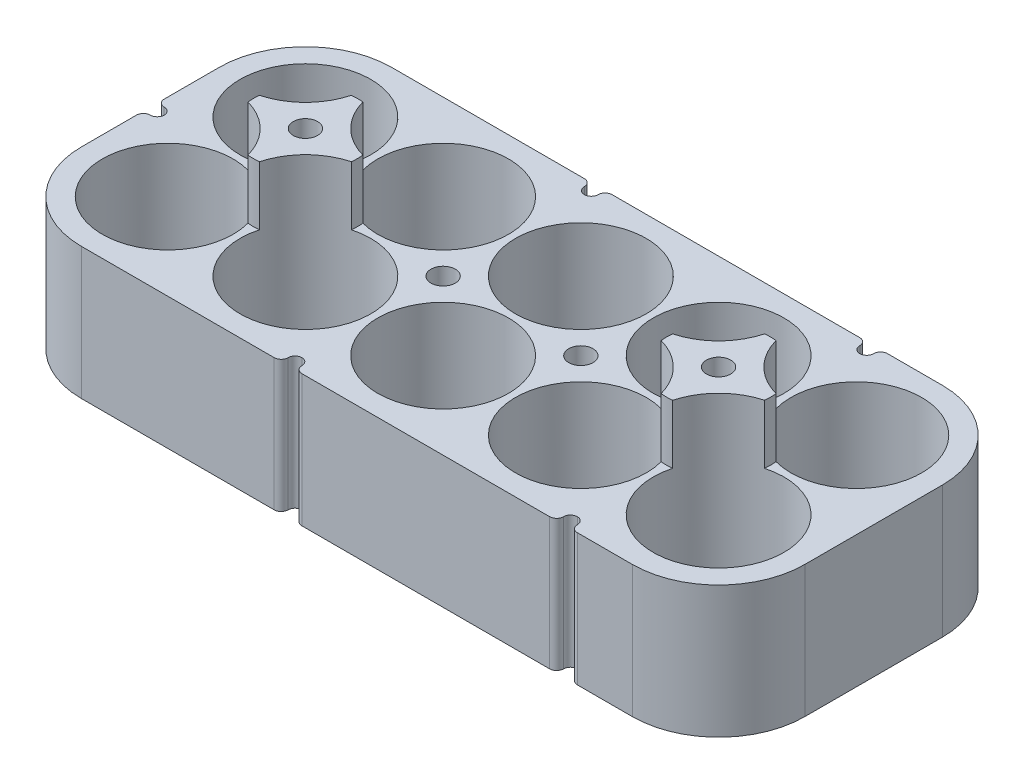
SolidWorks part; units mm, degrees
ref_plane "Front Plane" through (0, 0, 0) normal (0, 0, 1) x (1, 0, 0)
ref_plane "Top Plane" through (0, 0, 0) normal (0, 1, 0) x (1, 0, 0)
ref_plane "Right Plane" through (0, 0, 0) normal (1, 0, 0) x (0, 0, -1)
sketch "Sketch2" plane through (0, 0, 0) normal (0, 1, 0) x (1, 0, 0)
  line L0 (-39.7, 9.925) -> (-19.85, 9.925) construction
  line L1 (-19.85, 9.925) -> (0, 9.925) construction
  line L2 (0, 9.925) -> (19.85, 9.925) construction
  line L3 (19.85, 9.925) -> (39.7, 9.925) construction
  line L4 (39.7, 9.925) -> (39.7, -9.925) construction
  line L5 (39.7, -9.925) -> (19.85, -9.925) construction
  line L6 (19.85, -9.925) -> (0, -9.925) construction
  line L7 (0, -9.925) -> (-19.85, -9.925) construction
  line L8 (-39.7, 9.925) -> (-39.7, -9.925) construction
  line L9 (-39.7, -9.925) -> (-19.85, -9.925) construction
  line L10 (-39.7, 9.925) -> (39.7, -9.925) construction
  line L11 (-30.275, 9.925) -> (-29.275, 9.925) construction
  line L16 (-39.7, 0.5) -> (-39.7, -0.5) construction
  line L17 (-39.7, 22.35) -> (39.7, 22.35)
  line L19 (52.125, -9.925) -> (52.125, 9.925)
  line L20 (39.7, -22.35) -> (-39.7, -22.35)
  line L21 (-52.125, -9.925) -> (-52.125, 9.925)
  line L22 (-39.7, -9.925) -> (-52.125, -9.925) construction
  circle A0 centre (-39.7, 9.925) radius 9.425
  circle A1 centre (-19.85, 9.925) radius 9.425
  circle A2 centre (-39.7, -9.925) radius 9.425
  circle A3 centre (-19.85, -9.925) radius 9.425
  circle A4 centre (0, 9.925) radius 9.425
  circle A5 centre (0, -9.925) radius 9.425
  circle A6 centre (19.85, 9.925) radius 9.425
  circle A7 centre (19.85, -9.925) radius 9.425
  circle A8 centre (39.7, 9.925) radius 9.425
  circle A9 centre (39.7, -9.925) radius 9.425
  circle A10 centre (-39.7, 9.925) radius 12.425
  circle A11 centre (-39.7, -9.925) radius 12.425
  circle A12 centre (39.7, -9.925) radius 12.425
  circle A13 centre (39.7, 9.925) radius 12.425
  dimension "D1" = 18.85
  dimension "D2" = 1
  dimension "D3" = 1
  dimension "D4" = 3
extrude "Boss-Extrude1" add sketch "Sketch2" along normal blind 2.5 contours A13 L17 A10 A1 A11 A3 L20 A12 A7 A6 A5 A4 | A12 A13 A6 A8 | A13 A9 A12 A7 | A13 A12 L19 | A9 A13 A12 A8 | A11 A10 L21 | A11 A10 A1 A0 | A3 A11 A10 A2 | A10 A11 A0 A2 region at (-32.8744, 0, -19.9125) region at (0, 0, 0) region at (48.2539, 0, -18.4789) region at (-50.7094, 0, 0) region at (50.7094, 0, 0) region at (-50.5254, 0, 4.5259) region at (-39.7, 0, 0) region at (48.2539, 0, 18.4789) region at (39.7, 0, 0)
sketch "Sketch7" plane through (0, 0, 0) normal (0, 1, 0) x (1, 0, 0)
  line L0 (-29.775, 0) -> (-9.925, 0) construction
  line L1 (-9.925, 0) -> (9.925, 0) construction
  line L2 (9.925, 0) -> (29.775, 0) construction
  circle A1 centre (-29.775, 0) radius 3
  circle A2 centre (-9.925, 0) radius 1.75
  circle A3 centre (9.925, 0) radius 1.75
  circle A4 centre (29.775, 0) radius 3
  circle A5 centre (-29.775, 0) radius 4.6111 construction
  circle A7 centre (-39.7, 9.925) radius 9.425 construction
  circle A8 centre (-19.85, -9.925) radius 9.425 construction
  dimension "D1" = 6
  dimension "D2" = 3.5
extrude "Cut-Extrude3" cut sketch "Sketch7" along normal through all both and the other way through all
sketch "Sketch9" plane through (0, 2.5, 0) normal (0, 1, 0) x (1, 0, 0)
  line L0 (39.7, -22.35) -> (-39.7, -22.35)
  line L1 (-52.125, -9.925) -> (-52.125, 9.925)
  line L2 (-39.7, 22.35) -> (39.7, 22.35)
  line L3 (52.125, 9.925) -> (52.125, -9.925)
  line L4 (6.4609, 0) -> (-6.4609, 0) construction
  line L5 (6.4609, 0) -> (8.1929, -3)
  line L6 (8.1929, -3) -> (11.6571, -3)
  line L7 (11.6571, -3) -> (13.3891, 0)
  line L8 (13.3891, 0) -> (11.6571, 3)
  line L9 (11.6571, 3) -> (8.1929, 3)
  line L10 (8.1929, 3) -> (6.4609, 0)
  line L11 (-6.4609, 0) -> (-8.1929, 3)
  line L12 (-8.1929, 3) -> (-11.6571, 3)
  line L13 (-11.6571, 3) -> (-13.3891, 0)
  line L14 (-13.3891, 0) -> (-11.6571, -3)
  line L15 (-11.6571, -3) -> (-8.1929, -3)
  line L16 (-8.1929, -3) -> (-6.4609, 0)
  circle A0 centre (39.7, -9.925) radius 9.425
  circle A1 centre (19.85, -9.925) radius 9.425
  circle A2 centre (0, -9.925) radius 9.425
  circle A3 centre (-19.85, -9.925) radius 9.425
  circle A4 centre (-39.7, -9.925) radius 9.425
  circle A5 centre (-39.7, 9.925) radius 9.425
  circle A6 centre (-19.85, 9.925) radius 9.425
  circle A7 centre (0, 9.925) radius 9.425
  circle A8 centre (19.85, 9.925) radius 9.425
  circle A9 centre (39.7, 9.925) radius 9.425
  circle A10 centre (39.7, 9.925) radius 9.425 construction
  circle A11 centre (19.85, 9.925) radius 9.425 construction
  circle A12 centre (0, 9.925) radius 9.425 construction
  circle A13 centre (-19.85, 9.925) radius 9.425 construction
  circle A14 centre (-39.7, 9.925) radius 9.425 construction
  circle A15 centre (39.7, -9.925) radius 9.425 construction
  circle A16 centre (19.85, -9.925) radius 9.425 construction
  circle A17 centre (0, -9.925) radius 9.425 construction
  circle A18 centre (-19.85, -9.925) radius 9.425 construction
  circle A19 centre (-39.7, -9.925) radius 9.425 construction
  arc A20 (52.125, -9.925) -> (39.7, -22.35) centre (39.7, -9.925) cw
  arc A21 (-52.125, -9.925) -> (-39.7, -22.35) centre (-39.7, -9.925) ccw
  arc A22 (-52.125, 9.925) -> (-39.7, 22.35) centre (-39.7, 9.925) cw
  arc A23 (39.7, 22.35) -> (52.125, 9.925) centre (39.7, 9.925) cw
  circle A24 centre (29.775, 0) radius 3
  circle A25 centre (-29.775, 0) radius 3
  circle A26 centre (29.775, 0) radius 3 construction
  circle A27 centre (-29.775, 0) radius 3 construction
  circle A28 centre (9.925, 0) radius 3 construction
  circle A29 centre (9.925, 0) radius 1.75 construction
  circle A30 centre (-9.925, 0) radius 3 construction
  circle A31 centre (-9.925, 0) radius 1.75 construction
  dimension "D1" = 6
extrude "Boss-Extrude2" add sketch "Sketch9" along normal blind 3
sketch "Sketch11" plane through (0, 5.5, 0) normal (0, 1, 0) x (1, 0, 0)
  line L4 (39.7, -22.35) -> (-39.7, -22.35)
  line L17 (-52.125, -9.925) -> (-52.125, 9.925)
  line L18 (-39.7, 22.35) -> (39.7, 22.35)
  line L19 (52.125, 9.925) -> (52.125, -9.925)
  circle A10 centre (39.7, -9.925) radius 9.425
  circle A11 centre (19.85, -9.925) radius 9.425
  circle A12 centre (0, -9.925) radius 9.425
  circle A13 centre (-19.85, -9.925) radius 9.425
  circle A14 centre (-39.7, -9.925) radius 9.425
  circle A15 centre (-39.7, 9.925) radius 9.425
  circle A16 centre (-19.85, 9.925) radius 9.425
  circle A17 centre (0, 9.925) radius 9.425
  circle A18 centre (19.85, 9.925) radius 9.425
  circle A19 centre (39.7, 9.925) radius 9.425
  circle A26 centre (29.775, 0) radius 3
  circle A27 centre (-29.775, 0) radius 3
  circle A28 centre (-9.925, 0) radius 1.75
  circle A29 centre (9.925, 0) radius 1.75
  circle A30 centre (39.7, -9.925) radius 9.425 construction
  circle A31 centre (19.85, -9.925) radius 9.425 construction
  circle A32 centre (0, -9.925) radius 9.425 construction
  circle A33 centre (-19.85, -9.925) radius 9.425 construction
  circle A34 centre (-39.7, -9.925) radius 9.425 construction
  circle A35 centre (-39.7, 9.925) radius 9.425 construction
  circle A36 centre (-19.85, 9.925) radius 9.425 construction
  circle A37 centre (0, 9.925) radius 9.425 construction
  circle A38 centre (19.85, 9.925) radius 9.425 construction
  circle A39 centre (39.7, 9.925) radius 9.425 construction
  circle A40 centre (29.775, 0) radius 3 construction
  circle A41 centre (9.925, 0) radius 1.75 construction
  circle A42 centre (-9.925, 0) radius 1.75 construction
  circle A43 centre (-29.775, 0) radius 3 construction
  arc A44 (39.7, -22.35) -> (52.125, -9.925) centre (39.7, -9.925) ccw
  arc A45 (52.125, 9.925) -> (39.7, 22.35) centre (39.7, 9.925) ccw
  arc A46 (-39.7, 22.35) -> (-52.125, 9.925) centre (-39.7, 9.925) ccw
  arc A47 (-52.125, -9.925) -> (-39.7, -22.35) centre (-39.7, -9.925) ccw
extrude "Boss-Extrude3" add sketch "Sketch11" along normal blind 6
sketch "Sketch12" plane through (0, 11.5, 0) normal (0, 1, 0) x (1, 0, 0)
  line L0 (39.7, -22.35) -> (-39.7, -22.35)
  line L1 (-52.125, -9.925) -> (-52.125, 9.925)
  line L2 (-39.7, 22.35) -> (39.7, 22.35)
  line L3 (52.125, 9.925) -> (52.125, -9.925)
  circle A0 centre (39.7, -9.925) radius 9.425
  circle A1 centre (19.85, -9.925) radius 9.425
  circle A2 centre (0, -9.925) radius 9.425
  circle A3 centre (-19.85, -9.925) radius 9.425
  circle A4 centre (-39.7, -9.925) radius 9.425
  circle A5 centre (-39.7, 9.925) radius 9.425
  circle A6 centre (-19.85, 9.925) radius 9.425
  circle A7 centre (0, 9.925) radius 9.425
  circle A8 centre (19.85, 9.925) radius 9.425
  circle A9 centre (39.7, 9.925) radius 9.425
  circle A10 centre (39.7, 9.925) radius 9.425 construction
  circle A11 centre (19.85, 9.925) radius 9.425 construction
  circle A12 centre (0, 9.925) radius 9.425 construction
  circle A13 centre (-19.85, 9.925) radius 9.425 construction
  circle A14 centre (-39.7, 9.925) radius 9.425 construction
  circle A15 centre (39.7, -9.925) radius 9.425 construction
  circle A16 centre (19.85, -9.925) radius 9.425 construction
  circle A17 centre (0, -9.925) radius 9.425 construction
  circle A18 centre (-19.85, -9.925) radius 9.425 construction
  circle A19 centre (-39.7, -9.925) radius 9.425 construction
  circle A20 centre (29.775, 0) radius 1.75
  circle A21 centre (9.925, 0) radius 1.75
  circle A22 centre (-9.925, 0) radius 1.75
  circle A23 centre (-29.775, 0) radius 1.75
  circle A24 centre (9.925, 0) radius 1.75 construction
  circle A25 centre (-9.925, 0) radius 1.75 construction
  circle A26 centre (29.775, 0) radius 3 construction
  circle A27 centre (-29.775, 0) radius 3 construction
  arc A28 (39.7, -22.35) -> (52.125, -9.925) centre (39.7, -9.925) ccw
  arc A29 (52.125, 9.925) -> (39.7, 22.35) centre (39.7, 9.925) ccw
  arc A30 (-39.7, 22.35) -> (-52.125, 9.925) centre (-39.7, 9.925) ccw
  arc A31 (-52.125, -9.925) -> (-39.7, -22.35) centre (-39.7, -9.925) ccw
extrude "Boss-Extrude4" add sketch "Sketch12" along normal blind 16
ref_plane "Plane1" through (0, 22.5, 0) normal (0, 1, 0) x (1, 0, 0)
sketch "Sketch13" plane through (0, 22.5, 0) normal (0, 1, 0) x (1, 0, 0)
  line L0 (-26.3109, 0) -> (26.3109, 0) construction
  line L1 (-28.0429, -3) -> (-26.3109, 0)
  line L2 (-26.3109, 0) -> (-28.0429, 3)
  line L3 (-28.0429, 3) -> (-31.5071, 3)
  line L4 (-31.5071, 3) -> (-33.2391, 0)
  line L5 (-33.2391, 0) -> (-31.5071, -3)
  line L6 (-31.5071, -3) -> (-28.0429, -3)
  line L7 (28.0429, -3) -> (31.5071, -3)
  line L8 (31.5071, -3) -> (33.2391, 0)
  line L9 (33.2391, 0) -> (31.5071, 3)
  line L10 (31.5071, 3) -> (28.0429, 3)
  line L11 (28.0429, 3) -> (26.3109, 0)
  line L12 (26.3109, 0) -> (28.0429, -3)
  circle A0 centre (-29.775, 0) radius 3 construction
  circle A1 centre (29.775, 0) radius 3 construction
  dimension "D1" = 6
extrude "Cut-Extrude4" cut sketch "Sketch13" against normal blind 3
sketch "Sketch14" plane through (0, 27.5, 0) normal (0, 1, 0) x (1, 0, 0)
  line L0 (-52.125, 9.925) -> (-52.125, -9.925) construction
  line L1 (-52.125, 1) -> (-50.125, 1)
  line L2 (-52.125, 1) -> (-52.125, -1)
  line L3 (-52.125, -1) -> (-50.125, -1)
  line L4 (-50.125, 1) -> (-50.125, -1)
  line L5 (-39.7, -22.35) -> (39.7, -22.35) construction
  line L6 (28.775, -22.35) -> (30.775, -22.35)
  line L7 (28.775, -22.35) -> (28.775, -20.35)
  line L8 (28.775, -20.35) -> (30.775, -20.35)
  line L9 (30.775, -22.35) -> (30.775, -20.35)
  line L10 (39.7, 22.35) -> (-39.7, 22.35) construction
  line L11 (-10.925, -22.35) -> (-8.925, -22.35)
  line L12 (-10.925, -22.35) -> (-10.925, -20.35)
  line L13 (-10.925, -20.35) -> (-8.925, -20.35)
  line L14 (-8.925, -22.35) -> (-8.925, -20.35)
  line L15 (-10.925, 22.35) -> (-8.925, 22.35)
  line L16 (-10.925, 22.35) -> (-10.925, 20.35)
  line L17 (-10.925, 20.35) -> (-8.925, 20.35)
  line L18 (-8.925, 22.35) -> (-8.925, 20.35)
  line L19 (-9.925, 0) -> (-9.925, -20.35) construction
  line L20 (28.775, 22.35) -> (30.775, 22.35)
  line L21 (28.775, 22.35) -> (28.775, 20.35)
  line L22 (28.775, 20.35) -> (30.775, 20.35)
  line L23 (30.775, 22.35) -> (30.775, 20.35)
  line L24 (-9.925, 0) -> (-9.925, 20.35) construction
  line L25 (29.775, 0) -> (29.775, 20.35) construction
  line L26 (29.775, 0) -> (29.775, -20.35) construction
  line L27 (-50.125, 0) -> (-29.775, 0) construction
  dimension "D1" = 2
  dimension "D2" = 2
extrude "Cut-Extrude5" cut sketch "Sketch14" against normal through all
fillet "Fillet1" radius 1 30 edges at (28.775, 27.5, -21.35) (30.775, 27.5, -21.35) (-10.925, 27.5, -21.35) (-8.925, 27.5, -21.35) (-51.125, 27.5, 1) (-51.125, 27.5, -1) (30.775, 27.5, 21.35) (28.775, 27.5, 21.35) (-8.925, 27.5, 21.35) (-10.925, 27.5, 21.35) (28.775, 13.75, -20.35) (30.775, 13.75, -20.35) (-10.925, 13.75, -20.35) (-8.925, 13.75, -20.35) (-50.125, 13.75, 1) (-50.125, 13.75, -1) (30.775, 13.75, 20.35) (28.775, 13.75, 20.35) (30.775, 13.75, -22.35) (28.775, 13.75, -22.35) (-8.925, 13.75, -22.35) (-10.925, 13.75, -22.35) (-52.125, 13.75, 1) (-52.125, 13.75, -1) (30.775, 13.75, 22.35) (28.775, 13.75, 22.35) (-8.925, 13.75, 22.35) (-8.925, 13.75, 20.35) (-10.925, 13.75, 20.35) (-10.925, 13.75, 22.35)
ref_plane "Plane2" through (0, 19, 0) normal (0, 1, 0) x (1, 0, 0)
sketch "Sketch15" plane through (0, 19, 0) normal (0, 1, 0) x (1, 0, 0)
  line L0 (-52.125, 9.925) -> (-52.125, 2) construction
  line L1 (-52.125, 22.35) -> (52.125, 22.35)
  line L2 (-52.125, 22.35) -> (-52.125, -22.35)
  line L3 (-52.125, -22.35) -> (52.125, -22.35)
  line L4 (52.125, 22.35) -> (52.125, -22.35)
  line L5 (52.125, -9.925) -> (52.125, 9.925) construction
  line L6 (27.775, 22.35) -> (-7.925, 22.35) construction
  line L7 (-7.925, -22.35) -> (27.775, -22.35) construction
  circle A0 centre (-29.775, 0) radius 7.5
  circle A1 centre (29.775, 0) radius 7.5
  dimension "D1" = 15
extrude "Cut-Extrude6" cut sketch "Sketch15" along normal through all
sketch "Sketch16" plane through (0, 11.5, 0) normal (0, -1, 0) x (1, 0, 0)
  circle A0 centre (-29.775, 0) radius 3
  circle A1 centre (29.775, 0) radius 3
extrude "Boss-Extrude5" add sketch "Sketch16" against normal blind 0.3
